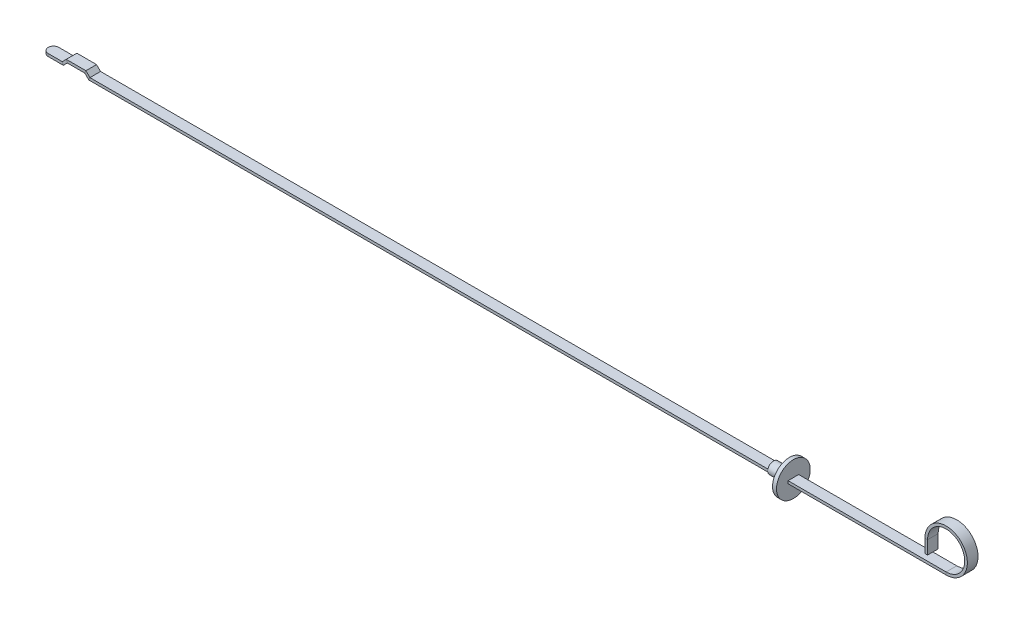
SolidWorks part; units mm, degrees
ref_plane "Płaszczyzna przednia" through (0, 0, 0) normal (0, 0, 1) x (1, 0, 0)
ref_plane "Płaszczyzna górna" through (0, 0, 0) normal (0, 1, 0) x (1, 0, 0)
ref_plane "Płaszczyzna prawa" through (0, 0, 0) normal (1, 0, 0) x (0, 0, -1)
sketch "Szkic1" plane through (0, 0, 0) normal (0, 0, 1) x (1, 0, 0)
  line L0 (0, 0) -> (125, 0)
  line L1 (110, 15) -> (110, 5)
  line L2 (0, 0) -> (-520, 0)
  line L3 (-520, 0) -> (-523, 3)
  line L4 (-523, 3) -> (-537, 3)
  line L5 (-537, 3) -> (-540, 0)
  line L6 (-540, 0) -> (-555, 0)
  arc A0 (125, 0) -> (110, 15) centre (125, 15) ccw
  dimension "D2" = 15
  dimension "D1" = 125
  dimension "D3" = 10
  dimension "D4" = 555
  dimension "D5" = 15
  dimension "D6" = 3
  dimension "D7" = 3
  dimension "D8" = 35
  dimension "D9" = 3
sketch "Szkic5" plane through (0, 0, 0) normal (0, 0, 1) x (1, 0, 0)
  line L1 (0, 6.35) -> (1, 6.35)
  line L3 (0, 0) -> (125, 0) construction
  line L5 (3, 6.35) -> (3, 0)
  line L6 (0, 0) -> (3, 0)
  line L7 (0, 6.35) -> (0, 4.35)
  line L8 (0, 4.35) -> (-9, 4.35)
  line L9 (-9, 4.35) -> (-9, 0)
  line L10 (-9, 0) -> (0, 0)
  arc A0 (1, 6.35) -> (3, 6.35) centre (2, 6.35) ccw
  dimension "D1" = 1
  dimension "D2" = 1
  dimension "D3" = 6.35
  dimension "D4" = 9
  dimension "D5" = 2
revolve "Obrót1" add sketch "Szkic5" angle 360 about L2
sketch "Szkic6" plane through (3, 0, 0) normal (1, 0, 0) x (0, 0, -1)
  circle A0 centre (0, 0) radius 12.7
  dimension "D1" = 25.4
extrude "Dodanie-wyciągnięcie3" add sketch "Szkic6" along normal blind 3
sketch "Szkic7" plane through (0, 0, 0) normal (1, 0, 0) x (0, 0, -1)
  line L1 (-4, -1) -> (4, -1)
  line L2 (-4, -1) -> (-4, 1)
  line L3 (-4, 1) -> (4, 1)
  line L4 (4, -1) -> (4, 1)
  line L5 (-4, -1) -> (4, 1) construction
  line L6 (-4, 1) -> (4, -1) construction
  point P0 (0, 0)
  dimension "D1" = 2
  dimension "D2" = 8
sweep "Wyciągnięcie po ścieżce1" add profiles "Szkic7" path "Szkic1"
fillet "Zaokrąglenie3" radius 4 2 edges at (-555, 0, -4) (-555, 0, 4)
